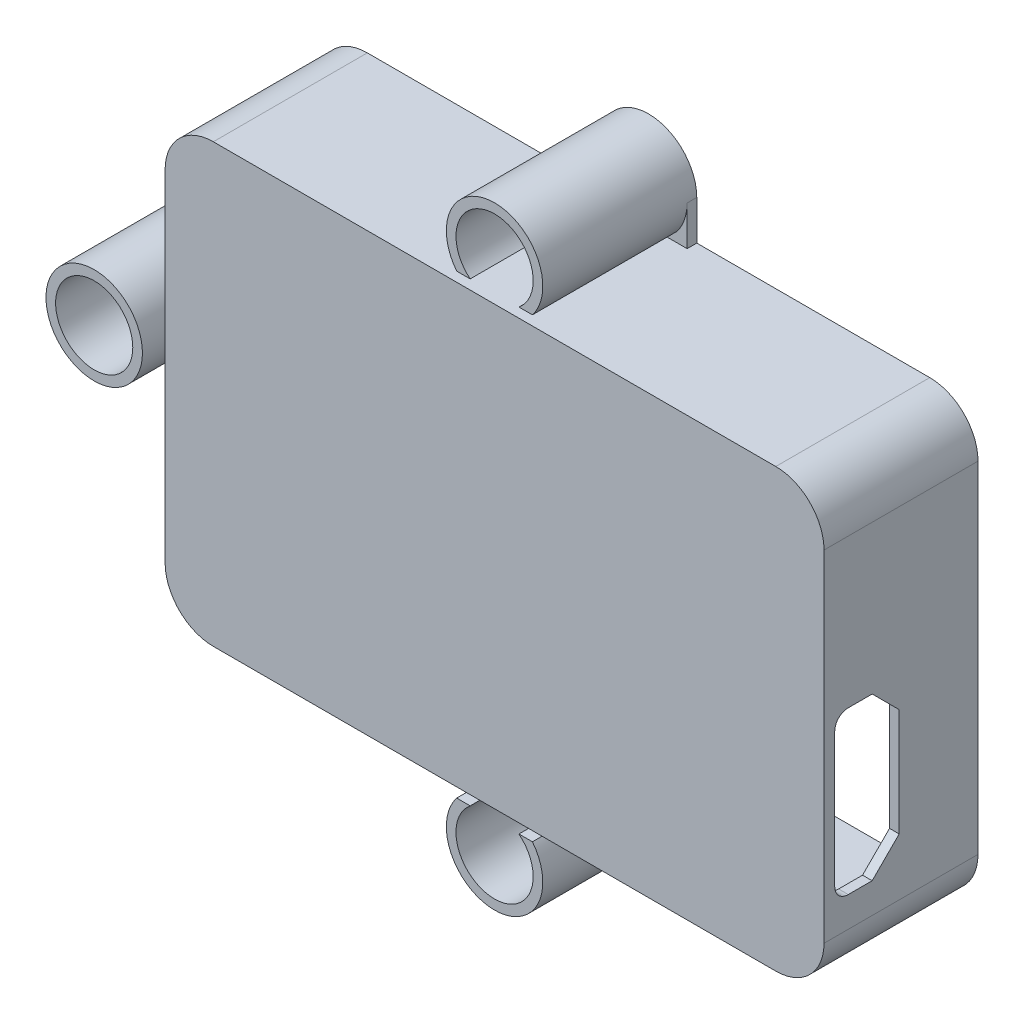
SolidWorks part; units mm, degrees
ref_plane "Front Plane" through (0, 0, 0) normal (0, 0, 1) x (1, 0, 0)
ref_plane "Top Plane" through (0, 0, 0) normal (0, 1, 0) x (1, 0, 0)
ref_plane "Right Plane" through (0, 0, 0) normal (1, 0, 0) x (0, 0, -1)
sketch "Sketch1" plane through (0, 0, 0) normal (0, 0, 1) x (1, 0, 0)
  line L1 (-14.575, -11.325) -> (14.575, -11.325)
  line L2 (-17.075, -8.825) -> (-17.075, 8.825)
  line L3 (-14.575, 11.325) -> (14.575, 11.325)
  line L4 (17.075, -8.825) -> (17.075, 8.825)
  line L5 (-17.075, -11.325) -> (17.075, 11.325) construction
  line L6 (-17.075, 11.325) -> (17.075, -11.325) construction
  line L8 (-16.575, 10.825) -> (-17.075, 10.825) construction
  line L9 (14.575, -10.825) -> (-14.575, -10.825)
  line L10 (16.575, -8.825) -> (16.575, 8.825)
  line L11 (14.575, 10.825) -> (-14.575, 10.825)
  line L12 (-16.575, -8.825) -> (-16.575, 8.825)
  line L13 (16.575, -10.825) -> (-16.575, 10.825) construction
  line L14 (16.575, 10.825) -> (-16.575, -10.825) construction
  line L15 (-16.575, 10.825) -> (-16.575, 11.325) construction
  line L16 (-16.375, 9.825) -> (-16.375, -9.825) construction
  line L17 (16.375, 9.825) -> (-16.375, 9.825) construction
  line L18 (-2.5, 13.375) -> (-2.5, 11.325)
  line L19 (2.5, 13.375) -> (2.5, 11.325)
  line L20 (-2.5, -13.375) -> (-2.5, -11.325)
  line L21 (2.5, -13.375) -> (2.5, -11.325)
  line L22 (-20.75, 2.5) -> (-17.075, 2.5)
  line L23 (-20.75, -2.5) -> (-17.075, -2.5)
  arc A0 (-14.575, -10.825) -> (-16.575, -8.825) centre (-14.575, -8.825) cw
  arc A1 (-2.4744, -13.0179) -> (2.4744, -13.0179) centre (0, -13.375) ccw construction
  arc A2 (14.575, -10.825) -> (16.575, -8.825) centre (14.575, -8.825) ccw
  arc A3 (16.575, 8.825) -> (14.575, 10.825) centre (14.575, 8.825) ccw
  arc A4 (-20.3929, 2.4744) -> (-20.3929, -2.4744) centre (-20.75, 0) ccw construction
  arc A5 (-14.575, 10.825) -> (-16.575, 8.825) centre (-14.575, 8.825) ccw
  arc A6 (-14.575, -11.325) -> (-17.075, -8.825) centre (-14.575, -8.825) cw
  arc A7 (14.575, -11.325) -> (17.075, -8.825) centre (14.575, -8.825) ccw
  arc A8 (2.4744, 13.0179) -> (-2.4744, 13.0179) centre (0, 13.375) ccw construction
  circle A9 centre (-20.75, 0) radius 1.25
  arc A10 (-2.4744, -13.0179) -> (2.4744, -13.0179) centre (0, -13.375) ccw
  circle A11 centre (0, 13.375) radius 1.25
  circle A12 centre (0, -13.375) radius 1.25
  arc A13 (-20.3929, 2.4744) -> (-20.3929, -2.4744) centre (-20.75, 0) ccw
  arc A14 (14.575, 11.325) -> (17.075, 8.825) centre (14.575, 8.825) cw
  arc A15 (-17.075, 8.825) -> (-14.575, 11.325) centre (-14.575, 8.825) cw
  arc A17 (2.4744, 13.0179) -> (-2.4744, 13.0179) centre (0, 13.375) ccw
  point P0 (0, 0)
  point P31 (0, 0)
  dimension "D4" = 2.5
  dimension "D5" = 2
  dimension "D6" = 2.5
  dimension "D1" = 0.5
  dimension "D2" = 0.2
  dimension "D3" = 1
extrude "Boss-Extrude1" add sketch "Sketch1" along normal offset from surface (7.48 mm away) 0.5 contours A13 L2 | L1 L4 L3 L2 L9 L12 L11 L10 | A17 L3 | A10 L1 region at (-16.053, -10.303, 0) region at (0, -11.3926, 0) region at (-18.9125, -2.4205, 0) region at (-2.4324, 12.35, 0) offset beyond the face yes
sketch "Sketch2" plane through (0, 0, 7.48) normal (0, 0, 1) x (1, 0, 0)
  line L0 (-2.5, 11.325) -> (2.5, 11.325)
  line L1 (-17.075, 2.5) -> (-17.075, -2.5)
  line L2 (-2.5, -11.325) -> (2.5, -11.325)
  line L13 (-17.075, 2.5) -> (-20.75, 2.5)
  line L14 (-20.75, -2.5) -> (-17.075, -2.5)
  line L15 (-17.075, -2.5) -> (-17.075, -8.825)
  line L16 (-14.575, -11.325) -> (-2.5, -11.325)
  line L17 (-2.5, -11.325) -> (-2.5, -13.375)
  line L18 (2.5, -13.375) -> (2.5, -11.325)
  line L19 (2.5, -11.325) -> (14.575, -11.325)
  line L20 (17.075, -8.825) -> (17.075, 8.825)
  line L21 (14.575, 11.325) -> (2.5, 11.325)
  line L22 (2.5, 11.325) -> (2.5, 13.375)
  line L23 (-2.5, 13.375) -> (-2.5, 11.325)
  line L24 (-2.5, 11.325) -> (-14.575, 11.325)
  line L25 (-17.075, 8.825) -> (-17.075, 2.5)
  line L26 (-17.075, 2.5) -> (-20.75, 2.5)
  line L27 (-20.75, -2.5) -> (-17.075, -2.5)
  line L28 (-17.075, -2.5) -> (-17.075, -8.825)
  line L29 (-14.575, -11.325) -> (-2.5, -11.325)
  line L30 (-2.5, -11.325) -> (-2.5, -13.375)
  line L31 (2.5, -13.375) -> (2.5, -11.325)
  line L32 (2.5, -11.325) -> (14.575, -11.325)
  line L33 (17.075, -8.825) -> (17.075, 8.825)
  line L34 (14.575, 11.325) -> (2.5, 11.325)
  line L35 (2.5, 11.325) -> (2.5, 13.375)
  line L36 (-2.5, 13.375) -> (-2.5, 11.325)
  line L37 (-2.5, 11.325) -> (-14.575, 11.325)
  line L38 (-17.075, 8.825) -> (-17.075, 2.5)
  arc A7 (-20.75, 2.5) -> (-20.75, -2.5) centre (-20.75, 0) ccw
  arc A8 (-17.075, -8.825) -> (-14.575, -11.325) centre (-14.575, -8.825) ccw
  arc A9 (-2.5, -13.375) -> (2.5, -13.375) centre (0, -13.375) ccw
  arc A10 (14.575, -11.325) -> (17.075, -8.825) centre (14.575, -8.825) ccw
  arc A11 (17.075, 8.825) -> (14.575, 11.325) centre (14.575, 8.825) ccw
  arc A12 (2.5, 13.375) -> (-2.5, 13.375) centre (0, 13.375) ccw
  arc A13 (-14.575, 11.325) -> (-17.075, 8.825) centre (-14.575, 8.825) ccw
  arc A14 (-20.75, 2.5) -> (-20.75, -2.5) centre (-20.75, 0) ccw
  arc A15 (-17.075, -8.825) -> (-14.575, -11.325) centre (-14.575, -8.825) ccw
  arc A16 (-2.5, -13.375) -> (2.5, -13.375) centre (0, -13.375) ccw
  arc A17 (14.575, -11.325) -> (17.075, -8.825) centre (14.575, -8.825) ccw
  arc A18 (17.075, 8.825) -> (14.575, 11.325) centre (14.575, 8.825) ccw
  arc A19 (2.5, 13.375) -> (-2.5, 13.375) centre (0, 13.375) ccw
  arc A20 (-14.575, 11.325) -> (-17.075, 8.825) centre (-14.575, 8.825) ccw
  arc M18 (-20.75, 2.5) -> (-20.75, -2.5) centre (-20.75, 0) ccw
  arc M23 (-2.5, -13.375) -> (2.5, -13.375) centre (0, -13.375) ccw
  arc M29 (2.5, 13.375) -> (-2.5, 13.375) centre (0, 13.375) ccw
  circle M57 centre (0, 13.375) radius 1.25
  circle M62 centre (-20.75, 0) radius 1.25
  line M63 (-17.075, 2.5) -> (-20.75, 2.5)
  line M64 (-20.75, -2.5) -> (-17.075, -2.5)
  line M68 (-2.5, -11.325) -> (-2.5, -13.375)
  line M69 (2.5, -13.375) -> (2.5, -11.325)
  line M74 (2.5, 11.325) -> (2.5, 13.375)
  line M75 (-2.5, 13.375) -> (-2.5, 11.325)
  circle M79 centre (0, -13.375) radius 1.25
  dimension "D1" = 0
extrude "Cut-Extrude1" cut sketch "Sketch2" against normal offset from surface (6.98 mm away) 0.5 contours L0 M75 M74 M29 M57 | L1 M63 M18 M64 M62 | L2 M68 M23 M69 M79 region at (-2.4324, 12.35, 7.48) region at (-17.1545, 0, 7.48) region at (2.4324, -12.35, 7.48) up to face at (-3.9075, 0, 0)
sketch "Sketch3" plane through (17.075, 0, 0) normal (1, 0, 0) x (0, 0, -1)
  line L0 (-5.98, -7.065) -> (-6.18, -7.065) construction
  line L1 (-7.425, -7.265) -> (-4.085, -7.265)
  line L2 (-7.425, -7.265) -> (-7.425, 1.115)
  line L3 (-7.425, 1.115) -> (-4.085, 1.115)
  line L4 (-4.085, -7.265) -> (-4.085, 1.115)
  line L5 (-7.225, -6.075) -> (-7.425, -6.075) construction
  line L6 (-6.18, -7.065) -> (-6.18, -7.265) construction
  line L7 (-6.18, 0.915) -> (-6.18, 1.115) construction
  line L8 (-4.285, -5.375) -> (-4.085, -5.375) construction
  dimension "D1" = 0.2
extrude "Cut-Extrude2" cut sketch "Sketch3" against normal up to next
chamfer "Chamfer1" distance 1.4 angle 45 2 edges at (16.825, 1.115, 4.085) (16.825, -7.265, 4.085)
fillet "Fillet1" radius 0.7 2 edges at (16.825, 1.115, 7.425) (16.825, -7.265, 7.425)
sketch "Sketch4" plane through (0, 0, 7.48) normal (0, 0, 1) x (1, 0, 0)
  line L4 (-17.075, 8.825) -> (-17.075, -8.825)
  line L5 (-14.575, -11.325) -> (14.575, -11.325)
  line L6 (17.075, -8.825) -> (17.075, 8.825)
  line L7 (14.575, 11.325) -> (-14.575, 11.325)
  line L8 (-17.075, 8.825) -> (-17.075, -8.825)
  line L9 (-14.575, -11.325) -> (14.575, -11.325)
  line L10 (17.075, -8.825) -> (17.075, 8.825)
  line L11 (14.575, 11.325) -> (-14.575, 11.325)
  arc A4 (-17.075, -8.825) -> (-14.575, -11.325) centre (-14.575, -8.825) ccw
  arc A5 (14.575, -11.325) -> (17.075, -8.825) centre (14.575, -8.825) ccw
  arc A6 (17.075, 8.825) -> (14.575, 11.325) centre (14.575, 8.825) ccw
  arc A7 (-14.575, 11.325) -> (-17.075, 8.825) centre (-14.575, 8.825) ccw
  arc A8 (-17.075, -8.825) -> (-14.575, -11.325) centre (-14.575, -8.825) ccw
  arc A9 (14.575, -11.325) -> (17.075, -8.825) centre (14.575, -8.825) ccw
  arc A10 (17.075, 8.825) -> (14.575, 11.325) centre (14.575, 8.825) ccw
  arc A11 (-14.575, 11.325) -> (-17.075, 8.825) centre (-14.575, 8.825) ccw
  dimension "D1" = 0
extrude "Boss-Extrude2" add sketch "Sketch4" along normal blind 0.5
sketch "Sketch5" plane through (0, 0, 0.5) normal (0, 0, 1) x (1, 0, 0)
  line L0 (2.5, -13.375) -> (2.5, -11.325) construction
  line L1 (2.5, -11.325) -> (-2.5, -11.325) construction
  line L2 (-2.5, -11.325) -> (-2.5, -13.375) construction
  line L3 (-2.5, 13.375) -> (-2.5, 11.325) construction
  line L4 (-2.5, 11.325) -> (2.5, 11.325) construction
  line L5 (2.5, 11.325) -> (2.5, 13.375) construction
  line L6 (-20.75, -2.5) -> (-17.075, -2.5) construction
  line L7 (-17.075, -2.5) -> (-17.075, 2.5) construction
  line L8 (-17.075, 2.5) -> (-20.75, 2.5) construction
  line L9 (2.5, -13.375) -> (2.5, -11.325)
  line L10 (2.5, -11.325) -> (-2.5, -11.325)
  line L11 (-2.5, -11.325) -> (-2.5, -13.375)
  line L12 (-2.5, 13.375) -> (-2.5, 11.325)
  line L13 (-2.5, 11.325) -> (2.5, 11.325)
  line L14 (2.5, 11.325) -> (2.5, 13.375)
  line L15 (-20.75, -2.5) -> (-17.075, -2.5)
  line L16 (-17.075, -2.5) -> (-17.075, 2.5)
  line L17 (-17.075, 2.5) -> (-20.75, 2.5)
  line L18 (-2.5, 11.825) -> (2.5, 11.825)
  line L19 (-20.75, 2) -> (-20.75, 2.5) construction
  line L20 (0, 11.825) -> (0, 11.325) construction
  line L21 (-17.075, 0) -> (17.075, 0) construction
  line L22 (17.075, -8.825) -> (17.075, 8.825) construction
  line L23 (-2.5, -11.825) -> (2.5, -11.825)
  arc A0 (-2.5, -13.375) -> (2.5, -13.375) centre (0, -13.375) ccw construction
  arc A1 (2.5, 13.375) -> (-2.5, 13.375) centre (0, 13.375) ccw construction
  arc A2 (-20.75, 2.5) -> (-20.75, -2.5) centre (-20.75, 0) ccw construction
  arc A3 (-2.5, -13.375) -> (2.5, -13.375) centre (0, -13.375) ccw
  arc A4 (2.5, 13.375) -> (-2.5, 13.375) centre (0, 13.375) ccw
  arc A5 (-20.75, 2.5) -> (-20.75, -2.5) centre (-20.75, 0) ccw
  circle A6 centre (-20.75, 0) radius 2
  circle A7 centre (-20.75, 0) radius 2.5
  circle A8 centre (0, 13.375) radius 2.5
  circle A9 centre (0, -13.375) radius 2.5
  circle A10 centre (0, 13.375) radius 2
  circle A11 centre (0, -13.375) radius 2
  arc M9 (-20.75, 2.5) -> (-20.75, -2.5) centre (-20.75, 0) ccw
  dimension "D1" = 0.5
extrude "Boss-Extrude3" add sketch "Sketch5" along normal up to surface (7.48 mm away) contours A10 L18 A8 A4 | A7 A6 M9 | A11 L23 A9 A3 region at (0, -15.8107, 0.5) region at (0, 15.8107, 0.5) region at (-23.1793, 0, 0.5) up to face at (0, 0, 7.98)
